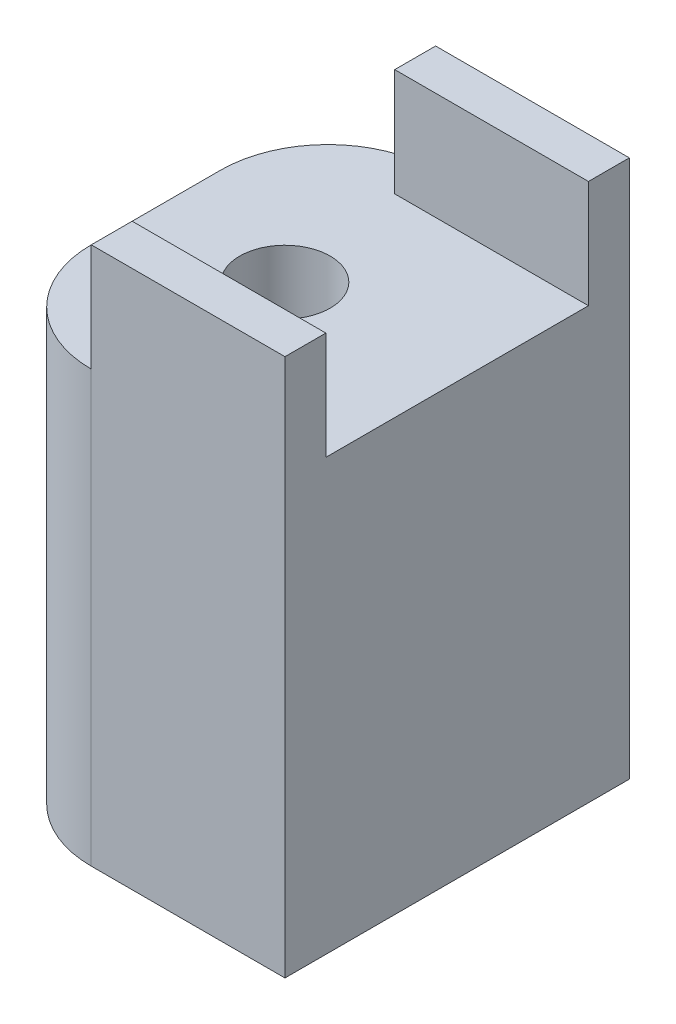
SolidWorks part; units mm, degrees
ref_plane "Front Plane" through (0, 0, 0) normal (0, 0, 1) x (1, 0, 0)
ref_plane "Top Plane" through (0, 0, 0) normal (0, 1, 0) x (1, 0, 0)
ref_plane "Right Plane" through (0, 0, 0) normal (1, 0, 0) x (0, 0, -1)
sketch "Sketch1" plane through (0, 0, 0) normal (0, 1, 0) x (1, 0, 0)
  line L5 (-6, 8) -> (6, 8)
  line L6 (-6, 8) -> (-6, -8)
  line L7 (-6, -8) -> (6, -8)
  line L8 (6, 8) -> (6, -8)
  line L9 (-6, 8) -> (6, -8) construction
  line L10 (-6, -8) -> (6, 8) construction
  line L11 (6, 8) -> (8, 8)
  line L12 (6, 8) -> (6, -8)
  line L13 (6, -8) -> (8, -8)
  line L14 (8, 8) -> (8, -8)
  circle A0 centre (0, 0) radius 2.1
  point P0 (0, 0)
  dimension "D1" = 4.2
  dimension "D2" = 16
  dimension "D3" = 6
  dimension "D4" = 2
extrude "Boss-Extrude1" add sketch "Sketch1" along normal blind 20 contours L8 L5 L6 L7 A0 | L14 L11 L8 L13 region at (0, 0, -7.8) region at (7, 0, 0)
fillet "Fillet1" radius 5 2 edges at (-6, 10, -8) (-6, 10, 8)
sketch "Sketch2" plane through (0, 20, 0) normal (0, 1, 0) x (1, 0, 0)
  line L0 (8, 0) -> (-6, 0) construction
  line L1 (8, 8) -> (-1, 8)
  line L2 (8, 8) -> (8, 6.1)
  line L3 (8, 6.1) -> (-1, 6.1)
  line L4 (-1, 8) -> (-1, 6.1)
  line L5 (8, 8) -> (8, -8) construction
  line L6 (-6, 3) -> (-6, -3) construction
  line L7 (-1, -8) -> (-1, -6.1)
  line L8 (8, -6.1) -> (-1, -6.1)
  line L9 (8, -8) -> (8, -6.1)
  line L10 (8, -8) -> (-1, -8)
  dimension "D1" = 1.9
extrude "Boss-Extrude2" add sketch "Sketch2" along normal blind 5
